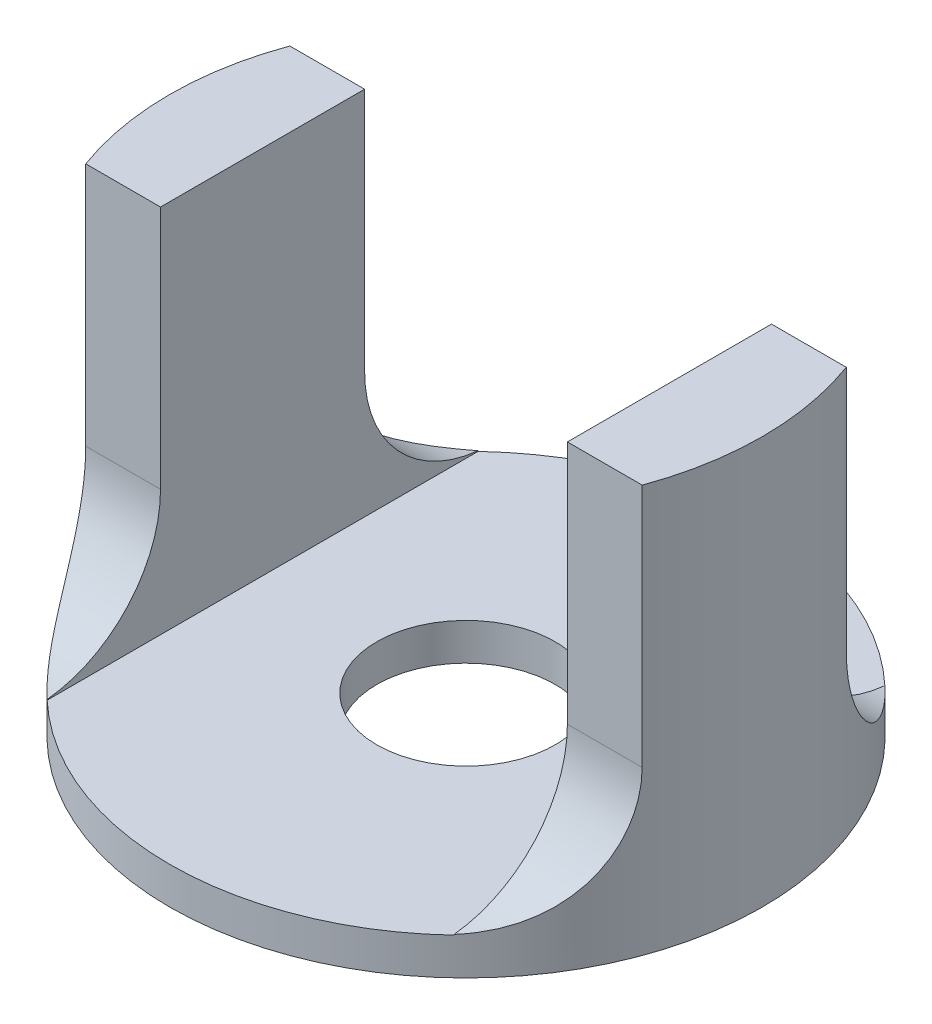
SolidWorks part; units mm, degrees
ref_plane "Front Plane" through (0, 0, 0) normal (0, 0, 1) x (1, 0, 0)
ref_plane "Top Plane" through (0, 0, 0) normal (0, 1, 0) x (1, 0, 0)
ref_plane "Right Plane" through (0, 0, 0) normal (1, 0, 0) x (0, 0, -1)
sketch "Sketch1" plane through (0, 0, 0) normal (0, 1, 0) x (1, 0, 0)
  circle A0 centre (0, 0) radius 101.6
  dimension "D1" = 203.2
extrude "Boss-Extrude1" add sketch "Sketch1" along normal blind 12.7
sketch "Sketch2" plane through (0, 12.7, 0) normal (0, 1, 0) x (1, 0, 0)
  line L0 (0, -148.3769) -> (0, 148.3769) construction
  line L1 (-191.7926, 0) -> (191.7926, 0) construction
  line L2 (69.7492, 34.9877) -> (95.3856, -34.9877) construction
  line L3 (-69.7492, -34.9877) -> (-95.3856, -34.9877)
  line L4 (-69.7492, -34.9877) -> (-69.7492, 34.9877)
  line L5 (-69.7492, 34.9877) -> (-95.3856, 34.9877)
  line L7 (-69.7492, -34.9877) -> (-95.3856, 34.9877) construction
  line L8 (-69.7492, 34.9877) -> (-95.3856, -34.9877) construction
  line L9 (69.7492, -34.9877) -> (95.3856, 34.9877) construction
  line L11 (69.7492, 34.9877) -> (95.3856, 34.9877)
  line L12 (69.7492, -34.9877) -> (95.3856, -34.9877)
  line L13 (69.7492, -34.9877) -> (69.7492, 34.9877)
  circle A0 centre (0, 0) radius 101.6 construction
  arc A1 (-95.3856, 34.9877) -> (-95.3856, -34.9877) centre (0, 0) ccw
  arc A2 (95.3856, -34.9877) -> (95.3856, 34.9877) centre (0, 0) ccw
  point P0 (-82.5674, 0)
  point P4 (0, 0)
  point P8 (0, 0)
  point P19 (82.5674, 0)
extrude "Boss-Extrude3" add sketch "Sketch2" along normal blind 127
fillet "Fillet3" radius 43.18 4 edges at (82.5674, 12.7, 34.9877) (82.5674, 12.7, -34.9877) (-82.5674, 12.7, -34.9877) (-82.5674, 12.7, 34.9877)
sketch "Sketch3" plane through (0, 12.7, 0) normal (0, 1, 0) x (1, 0, 0)
  circle A0 centre (0, 0) radius 30.611
extrude "Cut-Extrude1" cut sketch "Sketch3" against normal through all
